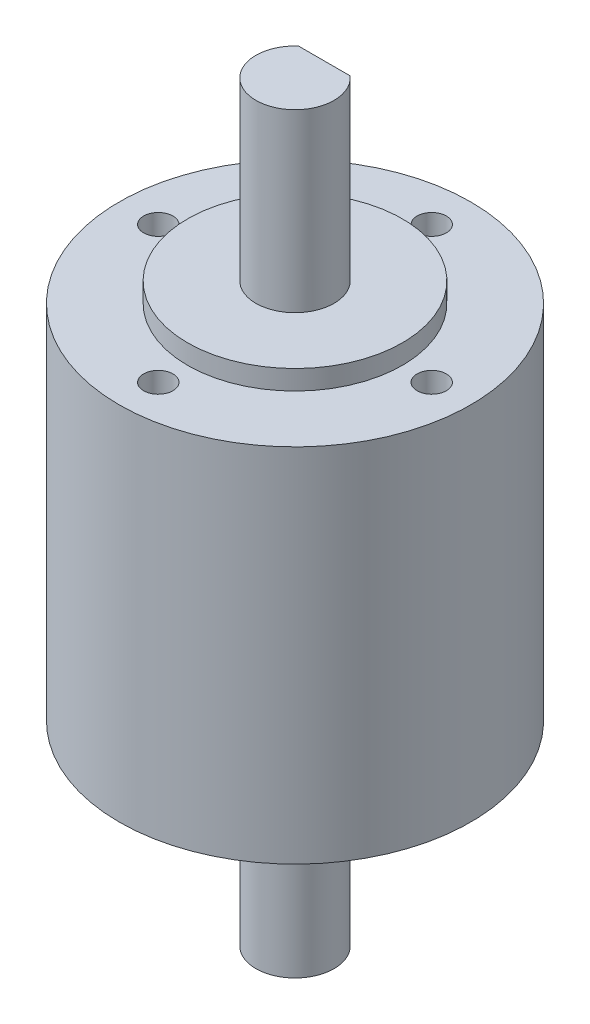
SolidWorks part; units mm, degrees
ref_plane "Front Plane" through (0, 0, 0) normal (0, 0, 1) x (1, 0, 0)
ref_plane "Top Plane" through (0, 0, 0) normal (0, 1, 0) x (1, 0, 0)
ref_plane "Right Plane" through (0, 0, 0) normal (1, 0, 0) x (0, 0, -1)
sketch "Sketch1" plane through (0, 0, 0) normal (0, 1, 0) x (1, 0, 0)
  circle A0 centre (0, 0) radius 18
  dimension "D1" = 36
extrude "Boss-Extrude1" add sketch "Sketch1" along normal mid plane 37
sketch "Sketch2" plane through (0, 18.5, 0) normal (0, 1, 0) x (1, 0, 0)
  circle A0 centre (0, 0) radius 11
  dimension "D1" = 22
extrude "Boss-Extrude2" add sketch "Sketch2" along normal blind 2
sketch "Sketch3" plane through (0, 20.5, 0) normal (0, 1, 0) x (1, 0, 0)
  circle A0 centre (0, 0) radius 4
  dimension "D1" = 8
extrude "Boss-Extrude4" add sketch "Sketch3" along normal blind 18
sketch "Sketch4" plane through (0, 38.5, 0) normal (0, 1, 0) x (1, 0, 0)
  line L0 (-2.6458, 3) -> (2.6458, 3)
  line L1 (0, -4) -> (0, 3) construction
  arc A0 (0, -4) -> (2.6458, 3) centre (0, 0) ccw construction
  circle A1 centre (0, 0) radius 4
  arc A2 (2.6458, 3) -> (-2.6458, 3) centre (0, 0) ccw
  arc A3 (-2.6458, 3) -> (0, -4) centre (0, 0) ccw construction
  point P8 (0, 2.0651)
  dimension "D2" = 7
  dimension "D1" = 0
extrude "Cut-Extrude1" cut sketch "Sketch4" against normal blind 15
sketch "Sketch5" plane through (0, 18.5, 0) normal (0, 1, 0) x (1, 0, 0)
  circle A0 centre (0, 0) radius 14 construction
  circle A1 centre (0, 14) radius 1.5
  circle A2 centre (-14, 0) radius 1.5
  circle A3 centre (0, -14) radius 1.5
  circle A4 centre (14, 0) radius 1.5
  dimension "D1" = 28
  dimension "D2" = 3
extrude "Cut-Extrude2" cut sketch "Sketch5" against normal blind 4
mirror "Mirror1" about plane through (0, 0, 0) normal (0, 1, 0) of "Cut-Extrude2", "Cut-Extrude1", "Boss-Extrude4", "Boss-Extrude2"
